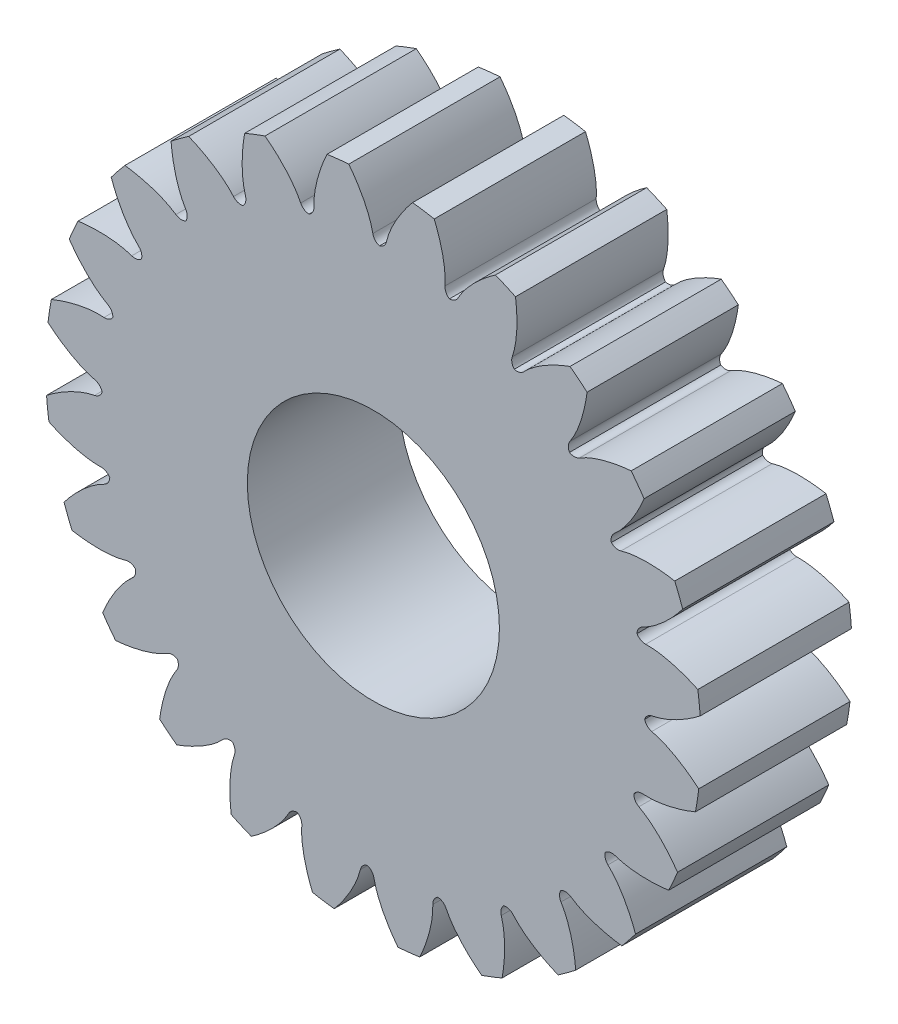
SolidWorks part; units mm, degrees
ref_plane "Front Plane" through (0, 0, 0) normal (0, 0, 1) x (1, 0, 0)
ref_plane "Top Plane" through (0, 0, 0) normal (0, 1, 0) x (1, 0, 0)
ref_plane "Right Plane" through (0, 0, 0) normal (1, 0, 0) x (0, 0, -1)
sketch "Sketch6" plane through (0, 0, 0) normal (0, 0, 1) x (1, 0, 0)
  circle A0 centre (0, 0) radius 2.5
  dimension "D1" = 5
sketch "Sketch7" plane through (0, 0, 0) normal (0, 0, 1) x (1, 0, 0)
  spline S0 degree 4 poles (5.4378, 0) (5.4403, 0) (5.4473, 0.0003) (5.4604, 0.0012) (5.4818, 0.0035) (5.5214, 0.0093) (5.5686, 0.0188) (5.6216, 0.0319) (5.6781, 0.0485) (5.7261, 0.0642) (5.7736, 0.0812) (5.8207, 0.0995) (5.8773, 0.123) (5.9446, 0.1534) (6.0223, 0.1917) (6.1093, 0.2387) (6.1966, 0.2902) (6.2814, 0.3439) (6.3657, 0.4015) (6.4462, 0.4596) (6.5282, 0.5233) (6.6031, 0.5838) (6.6851, 0.6552) (6.7507, 0.7139) (6.8352, 0.7952) (6.8845, 0.8443) (6.9414, 0.903) (6.9662, 0.9298) (6.9816, 0.9462) knots 0 0 0 0 0 0.005377 0.015084 0.028532 0.04661 0.092111 0.119476 0.146842 0.174209 0.201575 0.228941 0.256307 0.307035 0.361767 0.4165 0.471232 0.525964 0.580697 0.635429 0.690161 0.744894 0.799626 0.854358 0.909091 0.954545 1 1 1 1 1 construction
  spline S1 degree 4 poles (5.4378, 0) (5.4403, 0) (5.4473, 0.0003) (5.4604, 0.0012) (5.4818, 0.0035) (5.5214, 0.0093) (5.5686, 0.0188) (5.6216, 0.0319) (5.6781, 0.0485) (5.7261, 0.0642) (5.7736, 0.0812) (5.8207, 0.0995) (5.8773, 0.123) (5.9446, 0.1534) (6.0223, 0.1917) (6.1093, 0.2387) (6.1966, 0.2902) (6.2814, 0.3439) (6.3657, 0.4015) (6.4462, 0.4596) (6.5282, 0.5233) (6.6031, 0.5838) (6.6851, 0.6552) (6.7507, 0.7139) (6.8169, 0.7776) (6.8489, 0.8089) (6.8651, 0.8252) knots 0 0 0 0 0 0.005377 0.015084 0.028532 0.04661 0.092111 0.119476 0.146842 0.174209 0.201575 0.228941 0.256307 0.307035 0.361767 0.4165 0.471232 0.525964 0.580697 0.635429 0.690161 0.744894 0.799626 0.854358 0.909091 0.909091 0.909091 0.909091 0.909091
sketch "Sketch4" plane through (0, 0, 0) normal (0, 0, 1) x (1, 0, 0)
  line L0 (0, 0) -> (9.7065, 0) construction
  line L1 (8.9136, 0) -> (-8.9136, 0) construction
  line L2 (0, 0) -> (7.3606, 0.8015) construction
  circle A0 centre (0, 0) radius 5.4378 construction
  circle A1 centre (0, 0) radius 6 construction
  circle A2 centre (0, 0) radius 5.375
  circle A3 centre (0, 0) radius 6.5
  arc A4 (5.5277, 0.011) -> (5.3723, -0.1698) centre (5.5622, -0.1758) ccw
  arc A5 (5.4005, 1.179) -> (5.2098, 1.3222) centre (5.394, 1.3689) cw
  spline S0 degree 4 poles (-54.6636, 4999.0046) (4.0834, 37.7732) (4.5373, 0.4086) (5.0301, -0.0448) (5.4818, 0.0035) (5.5214, 0.0093) (5.5686, 0.0188) (5.6216, 0.0319) (5.6781, 0.0485) (5.7261, 0.0642) (5.7736, 0.0812) (5.8207, 0.0995) (5.8773, 0.123) (5.9446, 0.1534) (6.0223, 0.1917) (6.1093, 0.2387) (6.1966, 0.2902) (6.2814, 0.3439) (6.3657, 0.4015) (6.4462, 0.4596) (6.5282, 0.5233) (6.6031, 0.5838) (6.6851, 0.6552) (7.2012, 1.1167) (9.4445, 3.5803) (-49.5531, -55.0651) (3541.6957, 3536.7617) knots -0.938271 -0.938271 -0.938271 -0.938271 -0.938271 0.005377 0.015084 0.028532 0.04661 0.092111 0.119476 0.146842 0.174209 0.201575 0.228941 0.256307 0.307035 0.361767 0.4165 0.471232 0.525964 0.580697 0.635429 0.690161 0.744894 0.799626 0.854358 2.411191 2.411191 2.411191 2.411191 2.411191 only from (5.4378, 0) to (6.8651, 0.8252) construction
  spline S1 degree 4 poles (5.4005, 1.179) (5.4203, 1.1797) (5.4528, 1.18) (5.4979, 1.1788) (5.5554, 1.1748) (5.6057, 1.1698) (5.6558, 1.1634) (5.7057, 1.1557) (5.766, 1.1449) (5.8382, 1.1297) (5.9224, 1.109) (6.0175, 1.0818) (6.1139, 1.0503) (6.2082, 1.0162) (6.3014, 0.9787) (6.3683, 0.9498) (6.4131, 0.9292) (6.4347, 0.919) knots 0.04913 0.04913 0.04913 0.04913 0.04913 0.092111 0.119476 0.146842 0.174209 0.201575 0.228941 0.256307 0.307035 0.361767 0.4165 0.471232 0.525964 0.580697 0.631873 0.631873 0.631873 0.631873 0.631873
  spline S2 degree 4 poles (5.5277, 0.011) (5.5472, 0.0146) (5.579, 0.0213) (5.6227, 0.0322) (5.6781, 0.0485) (5.7261, 0.0642) (5.7736, 0.0812) (5.8207, 0.0995) (5.8773, 0.123) (5.9446, 0.1534) (6.0223, 0.1917) (6.1093, 0.2387) (6.1966, 0.2902) (6.2814, 0.3439) (6.3643, 0.4006) (6.4234, 0.4432) (6.4628, 0.473) (6.4817, 0.4875) knots 0.04913 0.04913 0.04913 0.04913 0.04913 0.092111 0.119476 0.146842 0.174209 0.201575 0.228941 0.256307 0.307035 0.361767 0.4165 0.471232 0.525964 0.580697 0.631873 0.631873 0.631873 0.631873 0.631873
  point P11 (5.9647, 0.6495)
  point P16 (5.9944, 0.258)
  dimension "D1" = 13
  dimension "D2" = 10.75
  dimension "D3" = 12
  dimension "D4" = 10.8757
  dimension "D5" = 0.19
  dimension "D6" = 0.3927
extrude "Boss-Extrude1" add sketch "Sketch4" along normal blind 3 contours A2 region at (0, 0, 0)
extrude "Boss-Extrude2" add sketch "Sketch4<3>" along normal blind 3 contours A4 S2 A3 S1 A5 A2 region at (5.8135, 0.6331, 0)
sketch "Sketch4<3>" plane through (0, 0, 0) normal (0, 0, 1) x (1, 0, 0) same geometry as "Sketch4"
pattern_circular "CirPattern1" count 24 over 360 about axis through (0, 0, 3) along (0, 0, -1) of "Boss-Extrude2" reverse direction yes
extrude "Cut-Extrude1" cut sketch "Sketch6" along normal through all
equation "\"m\"= 22.5 / 45mm'module"
equation "\"N\"= 24'number of teeth"
equation "\"a\"= 25deg'pressure angle"
equation "\"da\"= \"m\" * ( \"N\" + 2 )'addendum circle diameter"
equation "\"df\"= \"m\" * ( \"N\" - 2.5 )'dedendum circle diameter"
equation "\"db\"= \"m\" * \"N\" * cos ( \"a\" )'basic circle diameter"
equation "\"rb\"= \"db\" / 2'basic circle radius"
equation "\"s\"= \"m\" * pi / 2'pitch circle tooth thickness"
equation "\"r\"= \"m\" * 0.38'dedendum circle angle"
equation "\"B\"= \"d\" * 0.3'tooth width"
equation "\"d\"= 12mm"
equation "\"D3@Sketch4\"=\"d\""
equation "\"D4@Sketch4\"=\"db\""
equation "\"D1@Sketch4\"=\"da\""
equation "\"D2@Sketch4\"=\"df\""
equation "\"D5@Sketch4\"=\"r\""
equation "\"D6@Sketch4\"=\"s\"/2"
